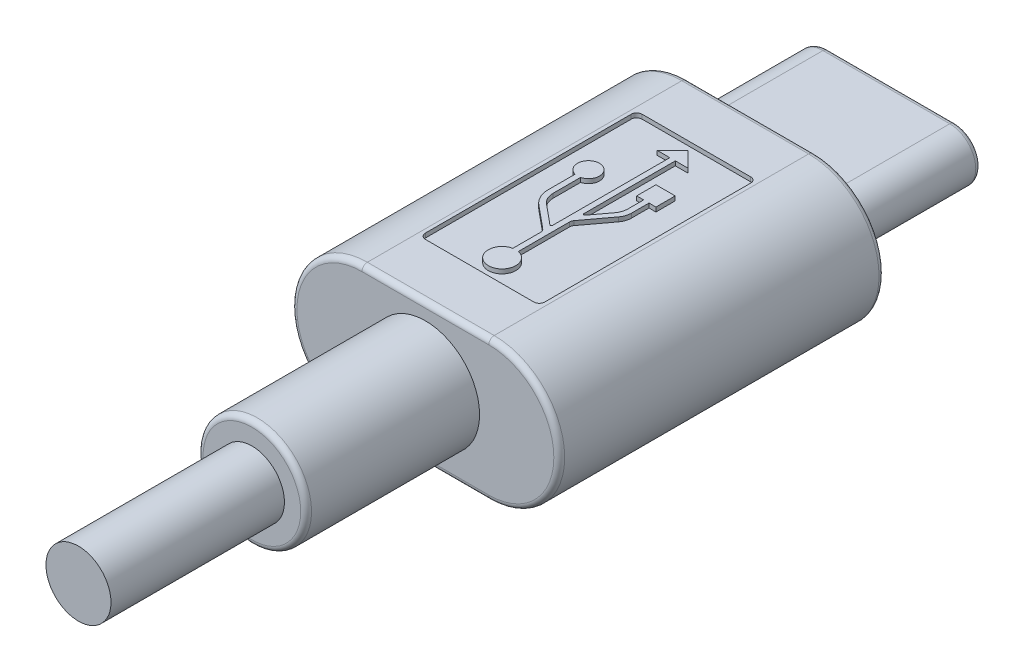
SolidWorks part; units mm, degrees
ref_plane "Спереди" through (0, 0, 0) normal (0, 0, 1) x (1, 0, 0)
ref_plane "Сверху" through (0, 0, 0) normal (0, 1, 0) x (1, 0, 0)
ref_plane "Справа" through (0, 0, 0) normal (1, 0, 0) x (0, 0, -1)
sketch "Эскиз1" plane through (0, 0, 0) normal (0, 0, 1) x (1, 0, 0)
  line L0 (-2.925, 0) -> (2.925, 0) construction
  line L1 (-2.925, 3.25) -> (2.925, 3.25)
  line L2 (-2.925, -3.25) -> (2.925, -3.25)
  arc A0 (-2.925, 3.25) -> (-2.925, -3.25) centre (-2.925, 0) ccw
  arc A1 (2.925, -3.25) -> (2.925, 3.25) centre (2.925, 0) ccw
  point P2 (0, 0)
  point P10 (90.6396, 0)
  dimension "D1" = 12.35
  dimension "D2" = 6.5
extrude "Бобышка-Вытянуть1" add sketch "Эскиз1" along normal blind 15
sketch "Эскиз2" plane through (0, 0, 0) normal (0, 0, -1) x (-1, 0, 0)
  line L0 (-2.925, 0) -> (2.925, 0) construction
  line L1 (-2.925, 1.2) -> (2.925, 1.2)
  line L2 (-2.925, -1.2) -> (2.925, -1.2)
  arc A0 (-2.925, 1.2) -> (-2.925, -1.2) centre (-2.925, 0) ccw
  arc A1 (2.925, -1.2) -> (2.925, 1.2) centre (2.925, 0) ccw
  point P2 (0, 0)
  point P10 (4.4573, 0)
  dimension "D1" = 8.25
  dimension "D2" = 2.4
extrude "Бобышка-Вытянуть2" add sketch "Эскиз2" along normal blind 6.51
sketch "Эскиз3" plane through (0, 0, -6.51) normal (0, 0, -1) x (-1, 0, 0)
  line L0 (3.415, 0.385) -> (3.415, -0.385) construction
  line L1 (-2.9446, -0.65) -> (2.9446, -0.65)
  line L3 (-2.9446, 0.65) -> (2.9446, 0.65)
  line L4 (3.415, -0.385) -> (3.415, 0.385)
  line L5 (0, 1.2) -> (0, -1.2) construction
  line L6 (2.925, 1.2) -> (-2.925, 1.2) construction
  line L7 (-2.925, -1.2) -> (2.925, -1.2) construction
  line L8 (-3.415, 0.385) -> (-3.415, -0.385) construction
  line L9 (-3.415, -0.385) -> (-3.415, 0.385)
  line L10 (-3.415, 0) -> (3.415, 0) construction
  arc A0 (3.415, 0.385) -> (2.9446, 0.65) centre (2.9446, 0.1) ccw
  arc A1 (2.9446, -0.65) -> (3.415, -0.385) centre (2.9446, -0.1) ccw
  arc A2 (-2.9446, -0.65) -> (-3.415, -0.385) centre (-2.9446, -0.1) cw
  arc A3 (-3.415, 0.385) -> (-2.9446, 0.65) centre (-2.9446, 0.1) cw
  point P0 (0, 0)
  point P22 (0, 0)
  dimension "D3" = 0.55
  dimension "D1" = 1.3
  dimension "D2" = 6.83
  dimension "D4" = 0.77
extrude "Вырез-Вытянуть1" cut sketch "Эскиз3" against normal blind 4.65
chamfer "Фаска1" distance 0.1 angle 45 8 edges at (3.2146, -0.5792, -6.51) (0, -0.65, -6.51) (-3.2146, -0.5792, -6.51) (-3.415, 0, -6.51) (-3.2146, 0.5792, -6.51) (0, 0.65, -6.51) (3.2146, 0.5792, -6.51) (3.415, 0, -6.51)
fillet "Скругление1" radius 0.25 4 edges at (-4.125, 0, -6.51) (0, -1.2, -6.51) (4.125, 0, -6.51) (0, 1.2, -6.51)
sketch "Эскиз4" plane through (0, 3.25, 0) normal (0, 1, 0) x (1, 0, 0)
  line L0 (0, -3.5745) -> (0, -12.5) construction
  line L1 (0, -2.8786) -> (-0.717, -3.5984)
  line L2 (0.635, -5.0007) -> (1.524, -5.0007)
  line L3 (0.635, -5.0007) -> (0.635, -5.8897)
  line L4 (0.635, -5.4452) -> (1.524, -5.4452) construction
  line L5 (0.635, -5.8897) -> (0.9547, -5.8897)
  line L6 (1.524, -5.0007) -> (1.524, -5.8897)
  line L7 (-0.127, -10.8386) -> (-0.127, -9.5633)
  line L8 (0.127, -10.8386) -> (0.127, -8.4746)
  line L9 (-0.717, -3.5984) -> (-0.127, -3.5984)
  line L10 (0.717, -3.5984) -> (0, -2.8786)
  line L11 (0, -2.8786) -> (0, -3.5126) construction
  line L12 (0.9547, -5.8897) -> (1.2043, -5.8897) construction
  line L13 (0.2185, -7.8495) -> (0.8034, -7.0654)
  line L14 (1.2043, -5.8897) -> (1.2043, -6.6932)
  line L15 (1.0531, -7.1488) -> (0.1774, -8.3227)
  line L16 (-0.2102, -9.0454) -> (-1.1205, -8.2928)
  line L17 (-1.397, -7.7055) -> (-1.397, -6.4451)
  line L18 (-1.651, -2.861) -> (-1.397, -2.861) construction
  line L19 (-0.2192, -9.3675) -> (-1.267, -8.5013)
  line L20 (-1.651, -7.6856) -> (-1.651, -6.4451)
  line L21 (-1.524, -2.861) -> (-1.524, -7.1582) construction
  line L22 (0.9547, -5.8897) -> (0.9547, -6.6098)
  line L23 (0.127, -7.6856) -> (-0.127, -7.6856) construction
  line L24 (0, -7.6856) -> (0, -7.968) construction
  line L25 (0.127, -3.5984) -> (0.717, -3.5984)
  line L26 (1.2043, -5.8897) -> (1.524, -5.8897)
  line L27 (-0.127, -9.0063) -> (-0.127, -3.5984)
  line L28 (0.127, -7.8191) -> (0.127, -3.5984)
  line L29 (0, -2.5) -> (0, -2.8786) construction
  line L30 (-2.5, -2.5) -> (2.5, -2.5)
  line L31 (-2.754, -2.754) -> (-2.754, -12.246)
  line L32 (-2.5, -12.5) -> (2.5, -12.5)
  line L33 (2.754, -2.754) -> (2.754, -12.246)
  line L34 (2.925, -15) -> (-2.925, -15) construction
  arc A0 (-0.127, -10.8386) -> (0.127, -10.8386) centre (0, -11.4608) ccw
  arc A1 (-1.397, -6.4451) -> (-1.651, -6.4451) centre (-1.524, -5.9532) ccw
  arc A2 (1.2043, -6.6932) -> (1.0531, -7.1488) centre (0.4423, -6.6932) cw
  arc A3 (0.9547, -6.6098) -> (0.8034, -7.0654) centre (0.1927, -6.6098) cw
  arc A4 (-1.397, -7.7055) -> (-1.1205, -8.2928) centre (-0.635, -7.7055) ccw
  arc A5 (-1.651, -7.6856) -> (-1.267, -8.5013) centre (-0.5927, -7.6856) ccw
  arc A6 (-0.127, -9.0063) -> (-0.2102, -9.0454) centre (-0.1778, -9.0063) cw
  arc A7 (0.127, -7.8191) -> (0.2185, -7.8495) centre (0.1778, -7.8191) ccw
  arc A8 (0.1774, -8.3227) -> (0.127, -8.4746) centre (0.381, -8.4746) ccw
  arc A9 (-0.127, -9.5633) -> (-0.2192, -9.3675) centre (-0.381, -9.5633) ccw
  arc A10 (2.5, -2.5) -> (2.754, -2.754) centre (2.5, -2.754) cw
  arc A11 (2.5, -12.5) -> (2.754, -12.246) centre (2.5, -12.246) ccw
  arc A12 (-2.754, -12.246) -> (-2.5, -12.5) centre (-2.5, -12.246) ccw
  arc A13 (-2.5, -2.5) -> (-2.754, -2.754) centre (-2.5, -2.754) ccw
  point P21 (0, 0)
  point P22 (0, 0)
  point P62 (-14.8899, 1.9934)
  point P63 (0, 0)
  point P64 (0, 0)
  point P73 (0, 0)
  point P74 (0, 0)
  point P75 (0, 0)
  point P76 (0, 0)
  point P77 (0, 0)
  point P78 (0, 0)
  point P79 (-14.6391, -8.1666)
  point P80 (-14.6419, 1.7394)
  point P81 (0, 0)
  point P82 (0, 0)
  point P83 (0, 0)
  point P84 (0, 0)
  point P85 (0, 0)
  point P86 (0, 0)
  point P87 (0, 0)
  point P88 (-13.4697, -4.2453)
  point P89 (0, 0)
  point P91 (0, 0)
  dimension "D1" = 1.27
  dimension "D2" = 1.016
  dimension "D12" = 0.762
  dimension "D15" = 0.25
  dimension "D16" = 0.762
  dimension "D18" = 0.0508
  dimension "D19" = 0.254
  dimension "D20" = 0.254
  dimension "D4" = 5.5076
  dimension "D26" = 1.0583
  dimension "D3" = 0.889
  dimension "D5" = 1.016
  dimension "D6" = 1.8975
  dimension "D7" = 7.8624
  dimension "D8" = 0.508
  dimension "D9" = 1.397
  dimension "D10" = 0.508
  dimension "D11" = 0.254
  dimension "D13" = 0.254
  dimension "D14" = 50.42
  dimension "D17" = 0.254
  dimension "D21" = 5
  dimension "D22" = 10
  dimension "D23" = 0.2497
  dimension "D24" = 1.0392
  dimension "D25" = 0.3786
  dimension "D27" = 2.9862
  dimension "D28" = 3.6416
  dimension "D29" = 1.126
  dimension "D30" = 2.5
extrude "Вырез-Вытянуть2" cut sketch "Эскиз4" against normal blind 0.2
sketch "Эскиз5" plane through (0, 0, 15) normal (0, 0, 1) x (1, 0, 0)
  circle A0 centre (0, 0) radius 2.5
  dimension "D1" = 5
extrude "Бобышка-Вытянуть3" add sketch "Эскиз5" along normal blind 8
fillet "Скругление2" radius 0.25 9 edges at (6.175, 0, 15) (0, -3.25, 15) (-6.175, 0, 15) (6.175, 0, 0) (0, -3.25, 0) (-6.175, 0, 0) (0, 3.25, 15) (0, 3.25, 0) (2.5, 0, 23)
sketch "Эскиз6" plane through (0, 0, 23) normal (0, 0, 1) x (1, 0, 0)
  circle A0 centre (0, 0) radius 1.5
  dimension "D1" = 3
extrude "Бобышка-Вытянуть4" add sketch "Эскиз6" along normal blind 8
